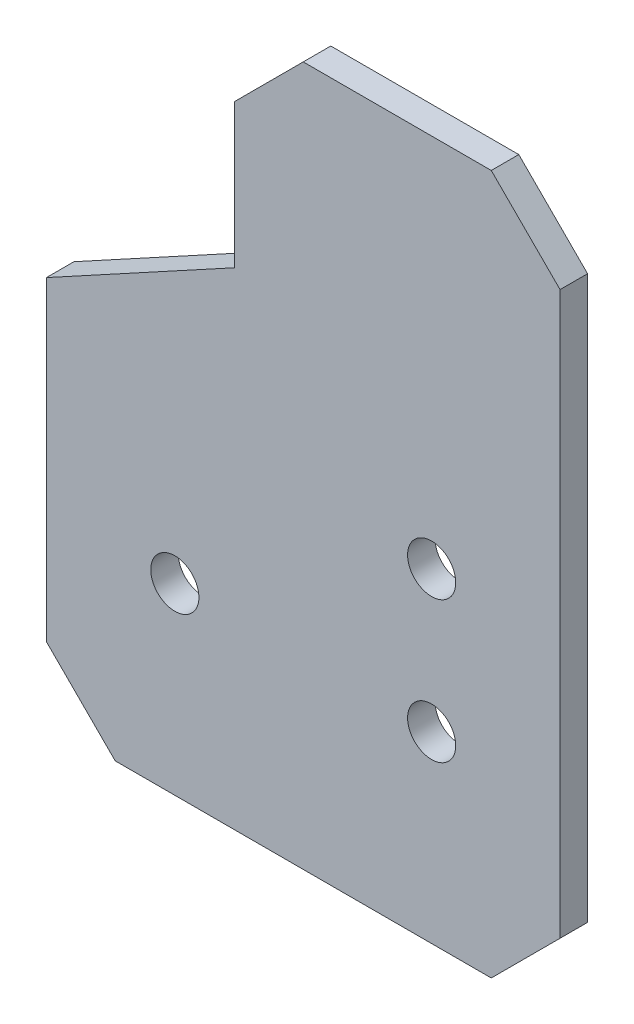
SolidWorks part; units mm, degrees
material "AISI 1020"
ref_plane "Спереди" through (0, 0, 0) normal (0, 0, 1) x (1, 0, 0)
ref_plane "Сверху" through (0, 0, 0) normal (0, 1, 0) x (1, 0, 0)
ref_plane "Справа" through (0, 0, 0) normal (1, 0, 0) x (0, 0, -1)
sketch "Эскиз1" plane through (0, 0, 0) normal (0, 0, 1) x (1, 0, 0)
  line L0 (-41, -102.5) -> (-56, -87.5) construction
  line L1 (56, -87.5) -> (41, -102.5) construction
  line L2 (-41, -102.5) -> (-56, -87.5)
  line L3 (56, -87.5) -> (41, -102.5)
  line L4 (41, -102.5) -> (-41, -102.5)
  line L5 (56, -87.5) -> (56, 35)
  line L6 (56, 35) -> (41, 50)
  line L7 (41, 50) -> (0, 50)
  line L8 (-15, 35) -> (-15, 3.6223)
  line L9 (-6.4685, 8.2738) -> (-56, -18.7316) construction
  line L10 (-15, 3.6223) -> (-56, -18.7316)
  line L11 (-56, -18.7316) -> (-56, -87.5)
  line L12 (-15, 27) -> (-15, 3) construction
  line L13 (571.7401, 50) -> (489.7401, 50) construction
  line L14 (586.7401, 35) -> (571.7401, 50) construction
  line L15 (0, 50) -> (-15, 35)
  line L16 (489.7401, 50) -> (474.7401, 35) construction
  circle A0 centre (-28, -62.5) radius 5.25 construction
  circle A1 centre (28, -62.5) radius 5.25 construction
  circle A2 centre (28, -31.7262) radius 5.25 construction
  circle A3 centre (-28, -62.5) radius 5.25
  circle A4 centre (28, -62.5) radius 5.25
  circle A5 centre (28, -31.7262) radius 5.25
base flange "Базовая кромка1" sketch "Эскиз1" thickness 6 reverse thickness direction no parameters "D1"=0.75
sketch "Сгиб-Линии1" [suppressed] plane through (0, 0, 0) normal (0, 1, 0) x (1, 0, 0)
sketch "Граничная рамка1" [suppressed] plane through (0, 0, 0) normal (0, 1, 0) x (1, 0, 0)
sheet metal parameters "Листовой металл3" thickness 6 parameters "D1"=0.75
flat pattern "Развертка3" [suppressed]
sketch "Сгиб-Линии2" plane through (0, 0, 0) normal (0, 1, 0) x (1, 0, 0)
sketch3d "Граничная рамка2" [suppressed]
  line L0 (56, 50, 0) -> (56, -102.5, 0) construction
  line L1 (-56, 50, 0) -> (-56, -102.5, 0) construction
  line L2 (56, 50, 0) -> (-56, 50, 0) construction
  line L3 (56, -102.5, 0) -> (-56, -102.5, 0) construction
